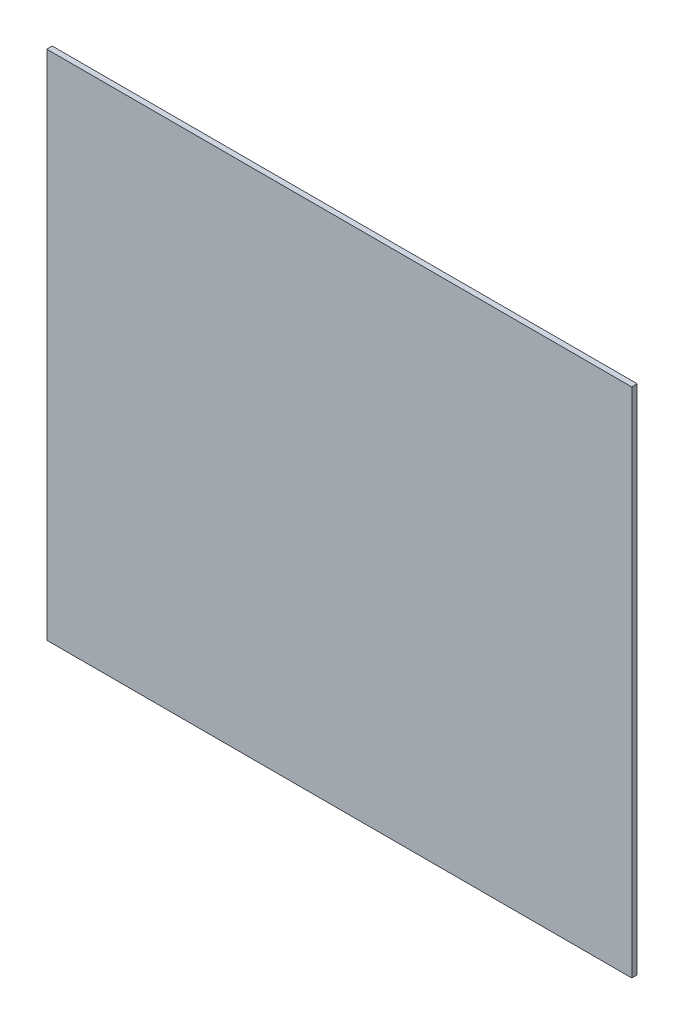
SolidWorks part; units mm, degrees
ref_plane "Front Plane" through (0, 0, 0) normal (0, 0, 1) x (1, 0, 0)
ref_plane "Top Plane" through (0, 0, 0) normal (0, 1, 0) x (1, 0, 0)
ref_plane "Right Plane" through (0, 0, 0) normal (1, 0, 0) x (0, 0, -1)
sketch "Sketch1" plane through (0, 0, 0) normal (0, 0, 1) x (1, 0, 0)
  line L1 (-160, -140) -> (160, -140)
  line L2 (-160, -140) -> (-160, 140)
  line L3 (-160, 140) -> (160, 140)
  line L4 (160, -140) -> (160, 140)
  line L5 (-160, -140) -> (160, 140) construction
  line L6 (-160, 140) -> (160, -140) construction
  point P0 (0, 0)
  dimension "D1" = 320
  dimension "D2" = 280
extrude "Boss-Extrude1" add sketch "Sketch1" along normal blind 3
equation "\"PCLength\"= 320mm'Length across I/O from PS to GPU"
equation "\"PCWidth\"= 242mm'Distance of longest part parallel to GPU(ussually GPU)"
equation "\"PCHeight\"= 172mm'Tallest point with mobo laying flat"
equation "\"WallThickness\"= 9mm'Thickness of each outer tank wall"
equation "\"ThermoBarrierThickness\"= 3mm'Thickness of barrier between hot side and cold side"
equation "\"HotSideGap\"= 25mm'Space in the hot side for a pump"
equation "\"PCClearance\"= 30mm'Clearance from top of tank to top of PC"
equation "\"RadiatorHeight\"= 275mm'Final Height from ground of radiators"
equation "\"D1@Sketch1\"=\"PCLength\""
equation "\"D2@Sketch1\"=\"RadiatorHeight\" + 5"
equation "\"D1@Boss-Extrude1\"=\"ThermoBarrierThickness\""
